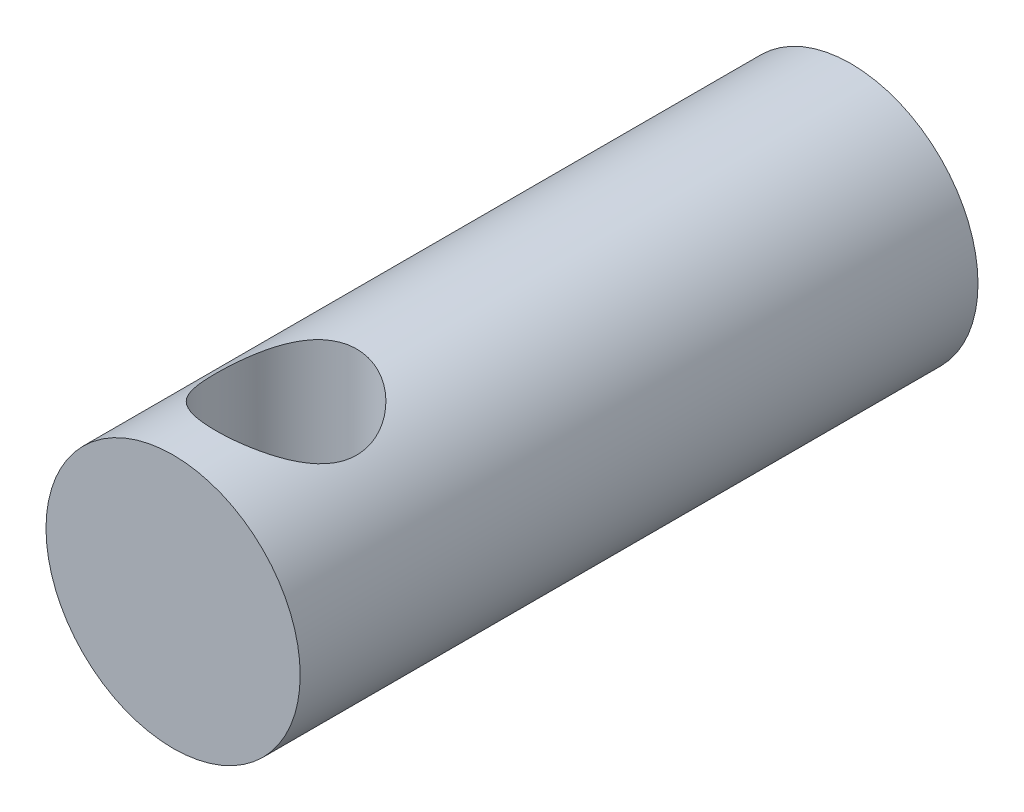
SolidWorks part; units mm, degrees
ref_plane "Front Plane" through (0, 0, 0) normal (0, 0, 1) x (1, 0, 0)
ref_plane "Top Plane" through (0, 0, 0) normal (0, 1, 0) x (1, 0, 0)
ref_plane "Right Plane" through (0, 0, 0) normal (1, 0, 0) x (0, 0, -1)
sketch "Sketch1" plane through (0, 0, 0) normal (0, 0, 1) x (1, 0, 0)
  circle A0 centre (0, 0) radius 7.1437
  dimension "D1" = 14.2875
extrude "Boss-Extrude1" add sketch "Sketch1" along normal blind 38.1
sketch "Sketch4" plane through (0, 0, 0) normal (0, 0, -1) x (-1, 0, 0)
  circle A0 centre (0, 0) radius 3.9688
  dimension "D1" = 7.9375
extrude "Cut-Extrude1" cut sketch "Sketch4" against normal blind 25.4
thread "Thread1" pitch 1.4111 method extrude profile "Thread Profile2" start angle 0, offset 0, length 25.4, pitch 1.4111, diameter 7.9375
ref_plane "Plane2" through (3.9688, 0, 0) normal (0, -1, 0) x (1, 0, 0)
sketch "Thread Profile2" plane through (3.9688, 0, 0) normal (0, -1, 0) x (1, 0, 0)
  line L0 (0, 0) -> (0, 1.4111) construction
  line L11 (0, 0) -> (0, 1.2347)
  line L12 (0, 1.2347) -> (-0.7638, 0.7937)
  line L13 (-0.7638, 0.7937) -> (-0.7638, 0.441)
  line L15 (-0.7638, 0.441) -> (0, 0)
  line L17 (-0.7638, 0.6174) -> (0, 0.6174) construction
  point P2 (0, 0)
  dimension "Pitch" = 1.4111
  dimension "Profile_Angle" = 60
  dimension "Profile_Land" = 0.3528
  dimension "Profile_Height" = 0.7638
sketch "Sketch7" plane through (0, 0, 0) normal (0, 1, 0) x (1, 0, 0)
  line L0 (7.1437, 0) -> (-7.1437, 0) construction
  circle A0 centre (0, -31.75) radius 3.9688
  point P4 (0.2699, -31.75)
  point P6 (0, 0)
  point P7 (0, 0)
  dimension "D2" = 7.9375
  dimension "D1" = 31.75
extrude "Cut-Extrude2" cut sketch "Sketch7" against normal through all both and the other way through all contours A0
